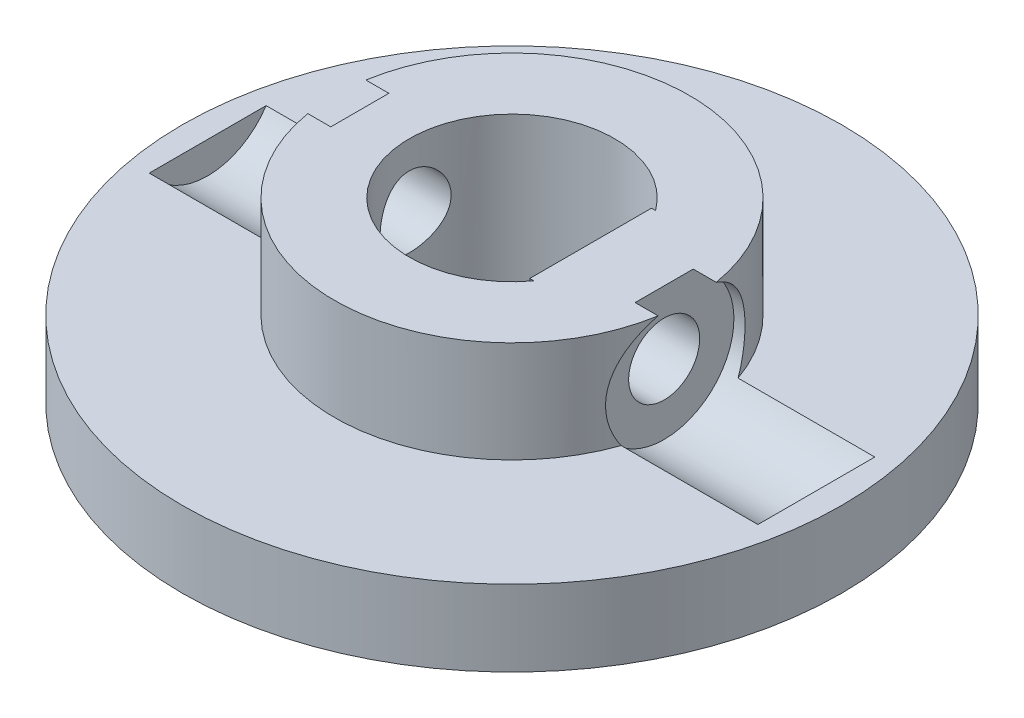
SolidWorks part; units mm, degrees
ref_plane "Front Plane" through (0, 0, 0) normal (0, 0, 1) x (1, 0, 0)
ref_plane "Top Plane" through (0, 0, 0) normal (0, 1, 0) x (1, 0, 0)
ref_plane "Right Plane" through (0, 0, 0) normal (1, 0, 0) x (0, 0, -1)
sketch "Stock_horn_drive_flange_profile" plane through (0, 0, 0) normal (0, 1, 0) x (1, 0, 0)
  circle A0 centre (0, 0) radius 13
  circle A1 centre (0, 0) radius 4.05
  dimension "D1" = 26
  dimension "D2" = 8.1
extrude "Stock_horn_drive_flange" add sketch "Stock_horn_drive_flange_profile" along normal blind 3 from offset 41
sketch "D_coupling_ring_profile" plane through (0, 0, 0) normal (0, 1, 0) x (1, 0, 0)
  circle A0 centre (0, 0) radius 7
  circle A1 centre (0, 0) radius 4.05
  dimension "D1" = 14
  dimension "D2" = 8.1
extrude "D_coupling_ring" add sketch "D_coupling_ring_profile" along normal blind 4 from offset 44
sketch "D_key_land_profile" plane through (0, 0, 0) normal (0, 1, 0) x (1, 0, 0)
  line L1 (3.1, -2.4) -> (6, -2.4)
  line L2 (3.1, -2.4) -> (3.1, 2.4)
  line L3 (3.1, 2.4) -> (6, 2.4)
  line L4 (6, -2.4) -> (6, 2.4)
  dimension "D1" = 2.9
  dimension "D2" = 4.8
  dimension "D3" = 3.1
  dimension "D4" = 2.4
extrude "D_key_land" add sketch "D_key_land_profile" along normal blind 4 from offset 44
sketch "Captured_horn_key_boss_profile" plane through (0, 0, 0) normal (0, 1, 0) x (1, 0, 0)
  circle A0 centre (0, 0) radius 13
  dimension "D1" = 26
extrude "Captured_horn_key_boss_SUPERSEDED_owned_servo" [suppressed] add sketch "Captured_horn_key_boss_profile" along normal blind 1.65 from offset 39.35
sketch "Stock_horn_pocket_Hub" plane through (0, 0, 0) normal (0, 1, 0) x (1, 0, 0)
  circle A0 centre (0, 0) radius 3.55
  dimension "D1" = 7.1
extrude "Key_pocket_Hub_SUPERSEDED_owned_servo" [suppressed] cut sketch "Stock_horn_pocket_Hub" along normal blind 1.65 from offset 39.35
sketch "Stock_horn_pocket_Horizontal" plane through (0, 0, 0) normal (0, 1, 0) x (1, 0, 0)
  line L1 (-8.15, -2.1) -> (8.15, -2.1)
  line L2 (-8.15, -2.1) -> (-8.15, 2.1)
  line L3 (-8.15, 2.1) -> (8.15, 2.1)
  line L4 (8.15, -2.1) -> (8.15, 2.1)
  dimension "D1" = 16.3
  dimension "D2" = 4.2
  dimension "D3" = 8.15
  dimension "D4" = 2.1
extrude "Key_pocket_Horizontal_SUPERSEDED_owned_servo" [suppressed] cut sketch "Stock_horn_pocket_Horizontal" along normal blind 1.65 from offset 39.35
sketch "Stock_horn_pocket_Vertical" plane through (0, 0, 0) normal (0, 1, 0) x (1, 0, 0)
  line L1 (-2.1, -8.15) -> (2.1, -8.15)
  line L2 (-2.1, -8.15) -> (-2.1, 8.15)
  line L3 (-2.1, 8.15) -> (2.1, 8.15)
  line L4 (2.1, -8.15) -> (2.1, 8.15)
  dimension "D1" = 4.2
  dimension "D2" = 16.3
  dimension "D3" = 2.1
  dimension "D4" = 8.15
extrude "Key_pocket_Vertical_SUPERSEDED_owned_servo" [suppressed] cut sketch "Stock_horn_pocket_Vertical" along normal blind 1.65 from offset 39.35
sketch "Stock_horn_pocket_Rounded_tips" plane through (0, 0, 0) normal (0, 1, 0) x (1, 0, 0)
  circle A0 centre (8.15, 0) radius 2.1
  circle A1 centre (-8.15, 0) radius 2.1
  circle A2 centre (0, 8.15) radius 2.1
  circle A3 centre (0, -8.15) radius 2.1
  dimension "D1" = 4.2
  dimension "D2" = 4.2
  dimension "D3" = 4.2
  dimension "D4" = 4.2
  dimension "D5" = 8.15
  dimension "D6" = 8.15
  dimension "D7" = 8.15
  dimension "D8" = 8.15
extrude "Key_pocket_Rounded_tips_SUPERSEDED_owned_servo" [suppressed] cut sketch "Stock_horn_pocket_Rounded_tips" along normal blind 1.65 from offset 39.35
sketch "Unmodified_horn_capture_M2_profile" plane through (0, 0, 0) normal (0, 1, 0) x (1, 0, 0)
  circle A0 centre (7, 7) radius 1.15
  circle A1 centre (-7, 7) radius 1.15
  circle A2 centre (-7, -7) radius 1.15
  circle A3 centre (7, -7) radius 1.15
  dimension "D1" = 2.3
  dimension "D2" = 2.3
  dimension "D3" = 2.3
  dimension "D4" = 2.3
  dimension "D5" = 7
  dimension "D6" = 7
  dimension "D7" = 7
  dimension "D8" = 7
extrude "Unmodified_horn_capture_M2_SUPERSEDED_owned_servo" [suppressed] cut sketch "Unmodified_horn_capture_M2_profile" along normal through all from offset 50 offset against normal yes
sketch "Horn_center_hub_clearance" plane through (0, 0, 0) normal (0, 1, 0) x (1, 0, 0)
  circle A0 centre (0, 0) radius 4
  dimension "D1" = 8
extrude "Hub_clearance_in_key_boss_only_SUPERSEDED_owned_servo" [suppressed] cut sketch "Horn_center_hub_clearance" along normal blind 1.65 from offset 39.35
sketch "Yaw_positive_retention_crossbolt_profile" plane through (0, 0, 0) normal (1, 0, 0) x (0, 0, -1)
  circle A0 centre (0, 45.5) radius 1.1
  dimension "D1" = 2.2
  dimension "D2" = 45.5
extrude "Yaw_positive_retention_crossbolt" cut sketch "Yaw_positive_retention_crossbolt_profile" along normal through all from offset 10 offset against normal yes
sketch "Crossbolt_flat_seat_-12" plane through (0, 0, 0) normal (1, 0, 0) x (0, 0, -1)
  circle A0 centre (0, 45.5) radius 2.75
  dimension "D1" = 5.5
  dimension "D2" = 45.5
extrude "Crossbolt_flat_seat_cut_-12" cut sketch "Crossbolt_flat_seat_-12" along normal blind 6 from offset 12 offset against normal yes
sketch "Crossbolt_flat_seat_6" plane through (0, 0, 0) normal (1, 0, 0) x (0, 0, -1)
  circle A0 centre (0, 45.5) radius 2.75
  dimension "D1" = 5.5
  dimension "D2" = 45.5
extrude "Crossbolt_flat_seat_cut_6" cut sketch "Crossbolt_flat_seat_6" along normal blind 6 from offset 6
sketch "SG90_spline_socket_boss_profile" plane through (0, 0, 0) normal (0, 1, 0) x (1, 0, 0)
  circle A0 centre (0, 0) radius 6
  dimension "D1" = 12
extrude "SG90_spline_socket_boss_OD12" add sketch "SG90_spline_socket_boss_profile" along normal blind 3.7 from offset 37.3
sketch "SG90_spline_press_socket_D4p85_depth2p5_profile" plane through (0, 0, 0) normal (0, 1, 0) x (1, 0, 0)
  circle A0 centre (0, 0) radius 2.425
  dimension "D1" = 4.85
extrude "SG90_spline_press_socket_D4p85_depth2p5" cut sketch "SG90_spline_press_socket_D4p85_depth2p5_profile" along normal blind 2.5 from offset 37.3
sketch "SG90_centre_screw_clearance_D2p4_profile" plane through (0, 0, 0) normal (0, 1, 0) x (1, 0, 0)
  circle A0 centre (0, 0) radius 1.2
  dimension "D1" = 2.4
extrude "SG90_centre_screw_clearance_D2p4" cut sketch "SG90_centre_screw_clearance_D2p4_profile" along normal blind 1.2 from offset 39.8
sketch "Crossbolt_axial_float_clearance_D2p8_profile" plane through (0, 0, 0) normal (1, 0, 0) x (0, 0, -1)
  circle A0 centre (0, 45.5) radius 1.4
  dimension "D1" = 2.8
extrude "Crossbolt_axial_float_clearance_D2p8" cut sketch "Crossbolt_axial_float_clearance_D2p8_profile" along normal through all from offset 10 offset against normal yes
